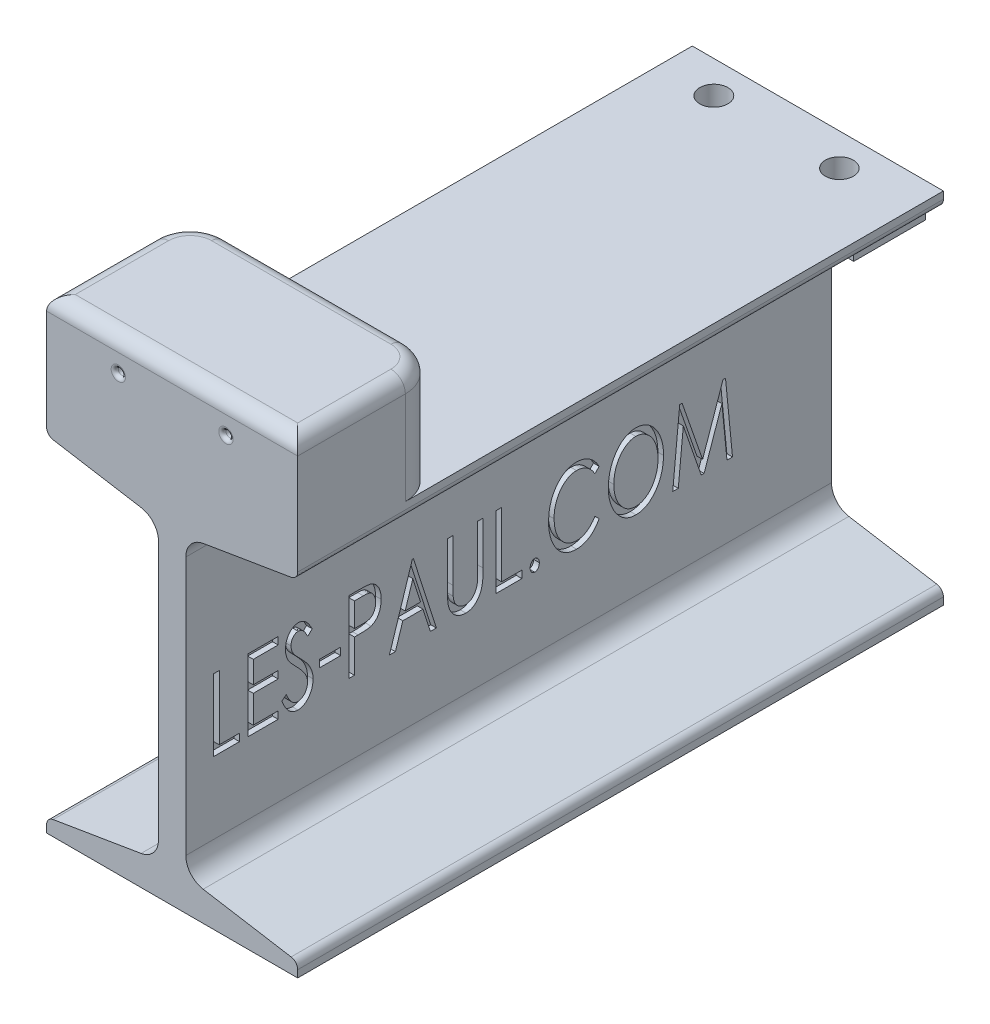
SolidWorks part; units mm, degrees
note: The reader was unsure of these and kept them because the rebuilt part matched: shared geometry of "Sketch47<4>".
material "AISI 1010 Steel, hot rolled bar"
ref_plane "Front Plane" through (0, 0, 0) normal (0, 0, 1) x (1, 0, 0)
ref_plane "Top Plane" through (0, 0, 0) normal (0, 1, 0) x (1, 0, 0)
ref_plane "Right Plane" through (0, 0, 0) normal (1, 0, 0) x (0, 0, -1)
sketch "Sketch1" plane through (0, 0, 0) normal (0, 0, 1) x (1, 0, 0)
  line L0 (0, -63.5) -> (0, 63.5) construction
  line L1 (-44.45, 63.5) -> (44.45, 63.5)
  line L2 (44.45, 63.5) -> (44.45, 60.96)
  line L3 (42.1152, 58.204) -> (10.9813, 53.0163)
  line L4 (4.826, 45.7505) -> (4.826, -45.7505)
  line L5 (10.9813, -53.0163) -> (42.1152, -58.204)
  line L6 (44.45, -60.96) -> (44.45, -63.5)
  line L7 (44.45, -63.5) -> (-44.45, -63.5)
  line L8 (-44.45, -60.96) -> (-44.45, -63.5)
  line L9 (-10.9813, -53.0163) -> (-42.1152, -58.204)
  line L10 (-4.826, 45.7505) -> (-4.826, -45.7505)
  line L11 (-42.1152, 58.204) -> (-10.9813, 53.0163)
  line L12 (-44.45, 63.5) -> (-44.45, 60.96)
  arc A0 (42.1152, -58.204) -> (44.45, -60.96) centre (41.656, -60.96) cw
  arc A1 (44.45, 60.96) -> (42.1152, 58.204) centre (41.656, 60.96) cw
  arc A2 (4.826, -45.7505) -> (10.9813, -53.0163) centre (12.192, -45.7505) ccw
  arc A3 (10.9813, 53.0163) -> (4.826, 45.7505) centre (12.192, 45.7505) ccw
  arc A4 (-10.9813, 53.0163) -> (-4.826, 45.7505) centre (-12.192, 45.7505) cw
  arc A5 (-4.826, -45.7505) -> (-10.9813, -53.0163) centre (-12.192, -45.7505) cw
  arc A6 (-44.45, 60.96) -> (-42.1152, 58.204) centre (-41.656, 60.96) ccw
  arc A7 (-42.1152, -58.204) -> (-44.45, -60.96) centre (-41.656, -60.96) ccw
  point P4 (0, 0)
  dimension "D3" = 2.794
  dimension "D4" = 7.366
  dimension "D1" = 127
  dimension "D2" = 44.45
  dimension "D5" = 9.46
  dimension "D6" = 9.46
  dimension "D7" = 2.54
  dimension "D8" = 2.54
  dimension "D9" = 4.826
extrude "Boss-Extrude1" add sketch "Sketch1" along normal mid plane 228.6
sketch "Sketch2" plane through (0, 63.5, 0) normal (0, 1, 0) x (1, 0, 0)
  line L0 (-44.45, -114.3) -> (-44.45, -63.5)
  line L1 (-44.45, -114.3) -> (-44.45, 114.3) construction
  line L2 (-44.45, -63.5) -> (44.45, -63.5)
  line L3 (44.45, -114.3) -> (44.45, 114.3) construction
  line L4 (44.45, -63.5) -> (44.45, -114.3)
  line L5 (44.45, -114.3) -> (-44.45, -114.3)
  dimension "D1" = 50.8
extrude "Boss-Extrude2" add sketch "Sketch2" along normal blind 38.1
fillet "Fillet4" radius 12.7 2 edges at (-44.45, 82.55, 63.5) (44.45, 82.55, 63.5)
fillet "Fillet5" radius 5.08 6 edges at (40.7303, 101.6, 67.2197) (0, 101.6, 63.5) (-40.7303, 101.6, 67.2197) (-44.45, 101.6, 95.25) (0, 101.6, 114.3) (44.45, 101.6, 95.25)
sketch "Sketch24" plane through (0, 0, 0) normal (0, 0, 1) x (1, 0, 0)
  line L0 (-10.9813, 53.0163) -> (-43.3872, 53.0163) construction
ref_plane "Plane2" through (0, 53.0163, 0) normal (0, 1, 0) x (1, 0, 0)
ref_plane "Plane4" through (0, -11.6213, 43.3713) normal (0, 0.2588, -0.9659) x (-1, 0, 0)
sketch "Sketch42" plane through (0, 141.2713, 63.5) normal (0, 0, 1) x (-1, 0, 0)
  line L0 (31.75, 44.7513) -> (-31.75, 44.7513) construction
  line L1 (44.45, 44.7513) -> (44.45, 77.7713) construction
  line L2 (0, 77.7713) -> (0, 44.7513) construction
  line L3 (-31.75, 77.7713) -> (31.75, 77.7713) construction
  circle A0 centre (19.05, 51.1013) radius 1.27
  circle A1 centre (-19.05, 51.1013) radius 1.27
  dimension "D1" = 2.54
  dimension "D3" = 6.35
  dimension "D2" = 25.4
extrude "Cut-Extrude3" cut sketch "Sketch42" against normal mid plane 177.8
fillet "Fillet8" radius 1.27 2 edges at (-20.32, 90.17, 114.3) (17.78, 90.17, 114.3)
sketch "Sketch45" plane through (0, 63.5, 0) normal (0, 1, 0) x (1, 0, 0)
  line L0 (-38.1, 114.3) -> (-38.1, 88.9)
  line L1 (44.45, 114.3) -> (-44.45, 114.3) construction
  line L2 (-38.1, 88.9) -> (38.1, 88.9)
  line L3 (38.1, 88.9) -> (38.1, 114.3)
  line L4 (38.1, 114.3) -> (-38.1, 114.3)
  line L5 (44.45, -76.2) -> (44.45, 114.3) construction
  line L6 (-44.45, -76.2) -> (-44.45, 114.3) construction
  dimension "D1" = 6.35
  dimension "D2" = 25.4
  dimension "D3" = 6.35
extrude "Boss-Extrude3" add sketch "Sketch45" against normal blind 12.065
sketch "Sketch47" plane through (0, 63.5, 0) normal (0, 1, 0) x (1, 0, 0)
  line L0 (0, 162.8047) -> (0, -29.721) construction
  line L1 (44.45, 114.3) -> (-44.45, 114.3) construction
  line L2 (-44.45, -76.2) -> (-44.45, 114.3) construction
  circle A0 centre (-25.4, 102.87) radius 5
  circle A2 centre (19.05, 102.87) radius 4.953
  dimension "D1" = 10
  dimension "D4" = 9.906
  dimension "D2" = 11.43
  dimension "D3" = 19.05
  dimension "D5" = 19.05
  dimension "D6" = 11.43
extrude "Cut-Extrude5" cut sketch "Sketch47" against normal up to surface (12.065 mm away) up to face at (22.8038, 51.435, -101.6)
sketch "Sketch51" plane through (4.826, 0, 0) normal (1, 0, 0) x (0, 0, -1)
  line L0 (-114.3, -45.7505) -> (-114.3, 45.7505) construction
  line L1 (-114.3, -45.7505) -> (114.3, -45.7505) construction
  text T0 "LES-PAUL.COM" font "Century Gothic" height 25.4
  dimension "D1" = 7.62
  dimension "D2" = 25.4
extrude "Cut-Extrude9" cut sketch "Sketch47<4>" against normal blind 25.4
sketch "Sketch47<4>" plane through (0, 63.5, 0) normal (0, 1, 0) x (1, 0, 0) same geometry as "Sketch47"
extrude "Cut-Extrude8" cut sketch "Sketch51" against normal blind 2
sketch "Sketch52" plane through (0, 51.435, 0) normal (0, -1, 0) x (1, 0, 0)
  line L0 (44.45, -114.3) -> (-44.45, -114.3) construction
  circle A0 centre (31.242, -102.87) radius 1.905
  circle A1 centre (19.05, -102.87) radius 4.953 construction
  dimension "D2" = 3.81
  dimension "D1" = 12.192
  dimension "D3" = 11.43
extrude "Cut-Extrude10" cut sketch "Sketch52" against normal blind 8.89
sketch "Sketch53" plane through (0, 51.435, 0) normal (0, -1, 0) x (1, 0, 0)
  line L0 (-7.5075, -114.3) -> (-38.1, -114.3) construction
  circle A0 centre (-13.208, -102.87) radius 1.905
  circle A1 centre (-25.4, -102.87) radius 5 construction
  dimension "D1" = 3.81
  dimension "D2" = 12.192
  dimension "D3" = 11.43
extrude "Cut-Extrude11" cut sketch "Sketch53" against normal blind 8.89
